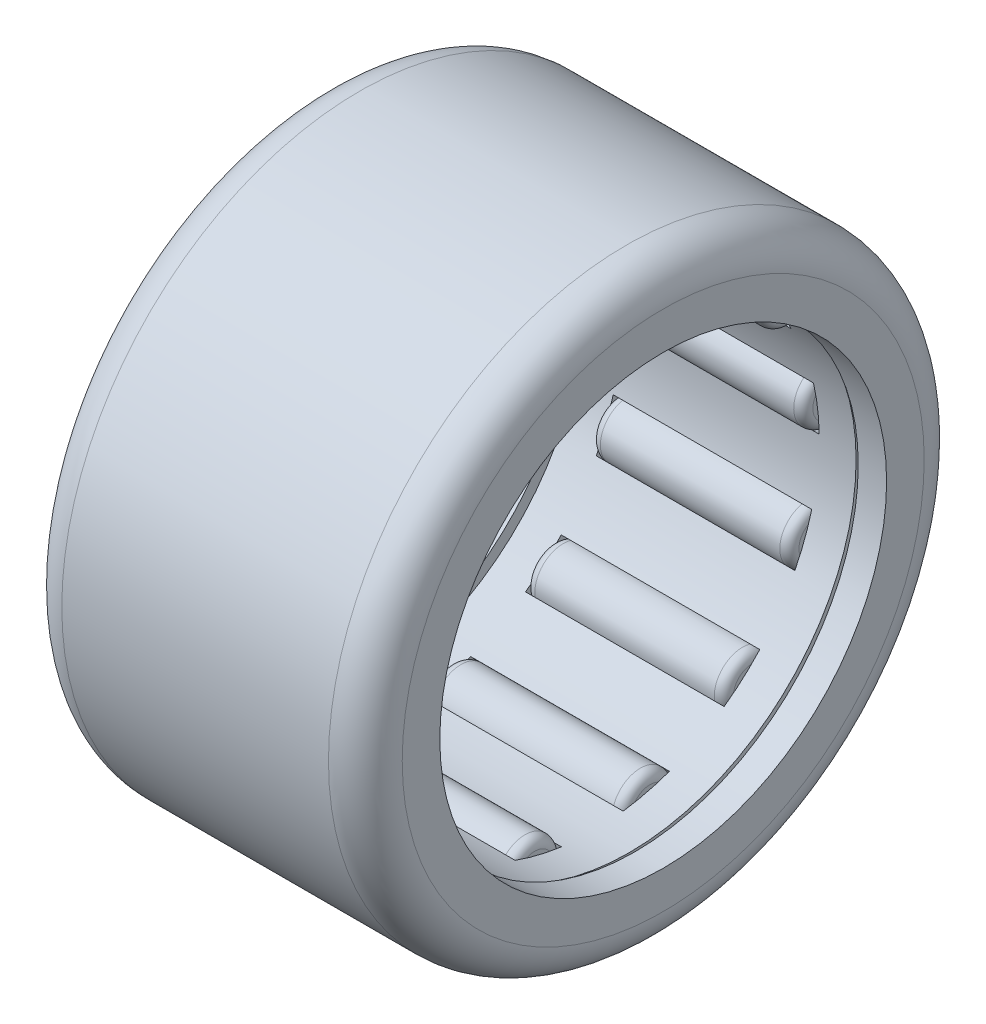
SolidWorks part; units mm, degrees
material "1.4301 (X5CrNi18-10)"
ref_plane "正面" through (0, 0, 0) normal (0, 0, 1) x (1, 0, 0)
ref_plane "平面" through (0, 0, 0) normal (0, 1, 0) x (1, 0, 0)
ref_plane "右側面" through (0, 0, 0) normal (1, 0, 0) x (0, 0, -1)
sketch "ｽｹｯﾁ1" plane through (0, 0, 0) normal (0, 0, 1) x (1, 0, 0)
  line L0 (0, 0) -> (11793.1943, 0) construction
  line L1 (6, 7.875) -> (5, 7.875)
  line L2 (-4.7, 10.5) -> (4.7, 10.5)
  line L3 (6, 9.2) -> (6, 7.875)
  line L4 (5, 7.875) -> (5, 9.2)
  line L5 (4.7, 9.5) -> (-4.7, 9.5)
  line L6 (0, 10.5) -> (0, 0) construction
  line L7 (-5, 7.875) -> (-5, 9.2)
  line L8 (-6, 9.2) -> (-6, 7.875)
  line L9 (-6, 7.875) -> (-5, 7.875)
  line L11 (-4.8, 8) -> (4.8, 8)
  line L12 (-4.8, 8) -> (-4.8, 9)
  line L13 (-4.8, 9) -> (4.8, 9)
  line L14 (4.8, 8) -> (4.8, 9)
  arc A0 (5, 9.2) -> (4.7, 9.5) centre (4.7, 9.2) ccw
  arc A1 (4.7, 10.5) -> (6, 9.2) centre (4.7, 9.2) cw
  arc A2 (-4.7, 10.5) -> (-6, 9.2) centre (-4.7, 9.2) ccw
  arc A3 (-5, 9.2) -> (-4.7, 9.5) centre (-4.7, 9.2) cw
  dimension "D1" = 1
  dimension "D2" = 15.75
  dimension "D8" = 1.3
  dimension "D3" = 19
  dimension "D4" = 1
  dimension "D5" = 9.6
  dimension "D6" = 12
  dimension "D7" = 16
revolve "回転1" add sketch "ｽｹｯﾁ1" angle 360 about L0
sketch "ｽｹｯﾁ3" plane through (0, 0, 0) normal (0, 0, 1) x (1, 0, 0)
  line L0 (-8.2223, 8.5) -> (49991.7777, 8.5) construction
  line L1 (4.8, 8) -> (4.8, 9) construction
  line L2 (-3.5, 8.5) -> (3.5, 8.5)
  line L3 (3.5, 8.5) -> (3.5, 9.1625)
  line L4 (3.1625, 9.5) -> (-3.1625, 9.5)
  line L5 (-3.5, 9.1625) -> (-3.5, 8.5)
  line L6 (0, 10.5) -> (0, 0) construction
  line L7 (-3.5, 8.5) -> (3.5, 8.5)
  line L9 (-3.5, 8.5) -> (-3.5, 9.5)
  line L10 (-3.5, 9.5) -> (3.5, 9.5)
  line L11 (3.5, 8.5) -> (3.5, 9.5)
  arc A0 (3.5, 9.1625) -> (3.1625, 9.5) centre (3.1625, 9.1625) ccw
  arc A1 (-3.1625, 9.5) -> (-3.5, 9.1625) centre (-3.1625, 9.1625) ccw
  point P4 (4.8, 8.5)
  point P11 (0, 8.5)
  dimension "D3" = 0.3375
  dimension "D1" = 7
  dimension "D2" = 2
revolve "ｶｯﾄ - 回転1" cut sketch "ｽｹｯﾁ3" angle 360 about L0
pattern_circular "円形ﾊﾟﾀｰﾝ2" count 13 over 360 about axis through (0, 0, 0) along (-1, 0, 0) of "ｶｯﾄ - 回転1"
revolve "回転2" add sketch "ｽｹｯﾁ3<4>" angle 360 about L0
sketch "ｽｹｯﾁ3<4>" plane through (0, 0, 0) normal (0, 0, 1) x (1, 0, 0) same geometry as "ｽｹｯﾁ3"
pattern_circular "円形ﾊﾟﾀｰﾝ4" count 13 over 360 about axis through (0, 0, 0) along (-1, 0, 0) of bodies 104
